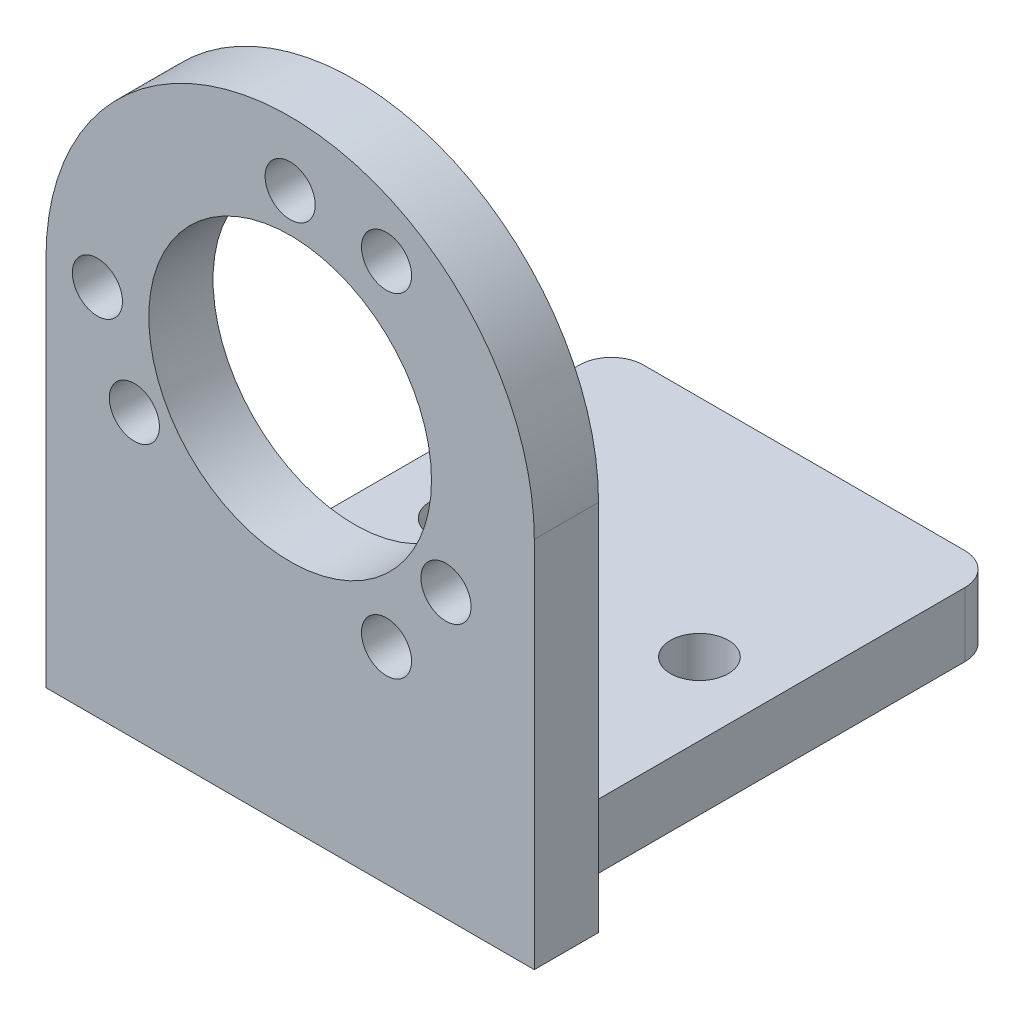
SolidWorks part; units mm, degrees
material "ABS"
ref_plane "Front Plane" through (0, 0, 0) normal (0, 0, 1) x (1, 0, 0)
ref_plane "Top Plane" through (0, 0, 0) normal (0, 1, 0) x (1, 0, 0)
ref_plane "Right Plane" through (0, 0, 0) normal (1, 0, 0) x (0, 0, -1)
sketch "Sketch1" plane through (0, 0, 0) normal (0, 0, 1) x (1, 0, 0)
  line L0 (-19, 0) -> (-19, -29)
  line L1 (-19, -29) -> (19, -29)
  line L2 (19, -29) -> (19, 0)
  circle A0 centre (0, 0) radius 19
  circle A1 centre (0, 0) radius 11
  dimension "D1" = 38
  dimension "D2" = 10
  dimension "D3" = 22
extrude "Boss-Extrude1" add sketch "Sketch1" along normal blind 5 contours A0 A1 | A0 L0 L1 L2 region at (0, -21.3225, 0) region at (0, 18.4626, 0)
sketch "Sketch2" plane through (0, 0, 0) normal (0, 0, -1) x (-1, 0, 0)
  line L1 (-15, -29) -> (15, -29)
  line L2 (-15, -29) -> (-15, -24)
  line L3 (-15, -24) -> (15, -24)
  line L4 (15, -29) -> (15, -24)
  line L5 (19, -29) -> (-19, -29) construction
  point P8 (0, -24)
  dimension "D1" = 5
  dimension "D2" = 30
extrude "Boss-Extrude2" add sketch "Sketch2" along normal blind 35
hole_wizard "M3 Clearance Hole1" positions "Sketch3" profile "Sketch4" hole size "M3" standard "ANSI Metric" end condition up to next
sketch "Sketch3" plane through (0, 0, 5) normal (0, 0, 1) x (1, 0, 0)
  line L0 (0, 0) -> (0, 14) construction
  line L2 (0, 0) -> (7.5, 12.9904) construction
  circle A0 centre (0, 0) radius 14 construction
  circle A1 centre (0, 0) radius 15 construction
  point P5 (0, 14)
  point P14 (12.1244, -7)
  point P15 (-12.1244, -7)
  point P19 (7.5, 12.9904)
  point P32 (7.5, -12.9904)
  point P33 (-15, 0)
  dimension "D1" = 28
  dimension "D2" = 3
  dimension "D3" = 30
  dimension "D4" = 30
sketch "Sketch4" plane through (-15, 0, 5) normal (1, 0, 0) x (0, -1, 0)
  line L0 (0, 0) -> (0, 5)
  line L1 (0, 5) -> (1.95, 5)
  line L2 (1.95, 5) -> (1.95, 0)
  line L5 (1.95, 0) -> (0, 0)
  line L11 (0, -6.35) -> (0, 107.95) construction
  dimension "Thru Hole Dia." = 3.9
  dimension "Thru Hole Depth" = 5
hole_wizard "M4 Clearance Hole1" positions "Sketch5" profile "Sketch6" hole size "M4" standard "ANSI Metric" end condition up to next
sketch "Sketch5" plane through (0, -24, 0) normal (0, 1, 0) x (1, 0, 0)
  line L0 (9.35, 17.5) -> (-9.35, 17.5) construction
  line L1 (-15, 35) -> (15, 35) construction
  point P1 (-9.35, 17.5)
  point P20 (9.35, 17.5)
  point P24 (0, 17.5)
  dimension "D1" = 18.7
  dimension "D2" = 17.5
sketch "Sketch6" plane through (-9.35, -24, -17.5) normal (1, 0, 0) x (0, 0, 1)
  line L0 (0, 0) -> (0, 5)
  line L1 (0, 5) -> (2.25, 5)
  line L2 (2.25, 5) -> (2.25, 0)
  line L5 (2.25, 0) -> (0, 0)
  line L11 (0, -6.35) -> (0, 107.95) construction
  dimension "Thru Hole Dia." = 4.5
  dimension "Thru Hole Depth" = 5
fillet "Fillet1" radius 2.5 5 edges at (-15, -26.5, -35) (15, -26.5, -35) (0, -24, 0) (-15, -26.5, 0) (15, -26.5, 0)
